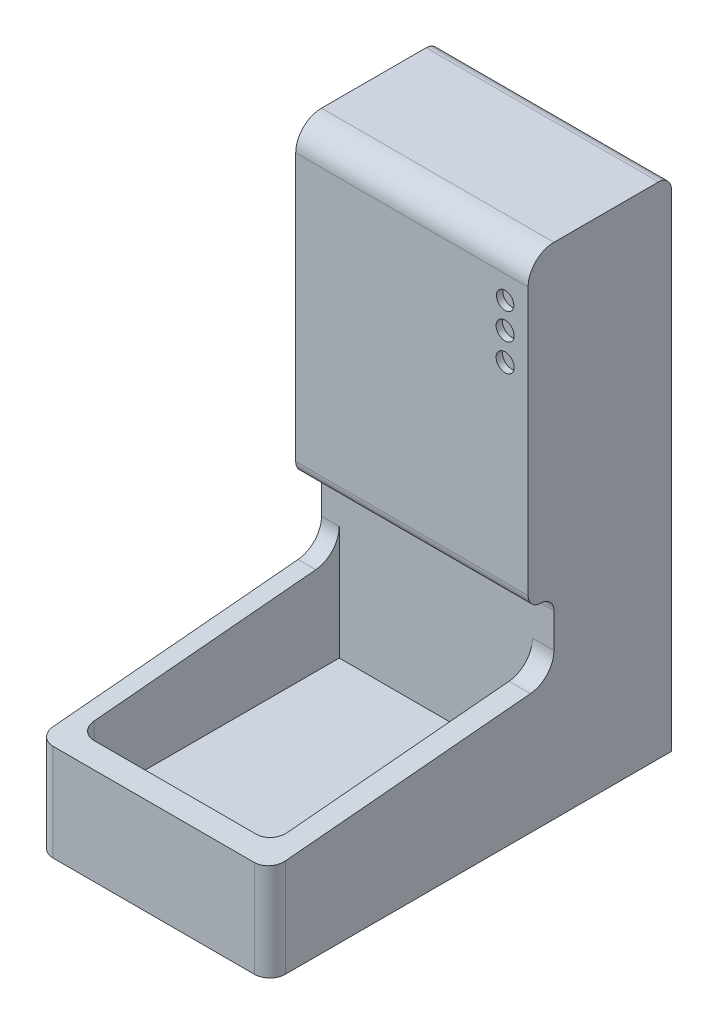
SolidWorks part; units mm, degrees
ref_plane "Front Plane" through (0, 0, 0) normal (0, 0, 1) x (1, 0, 0)
ref_plane "Top Plane" through (0, 0, 0) normal (0, 1, 0) x (1, 0, 0)
ref_plane "Right Plane" through (0, 0, 0) normal (1, 0, 0) x (0, 0, -1)
sketch "Sketch1" plane through (0, 0, 0) normal (1, 0, 0) x (0, 0, -1)
  line L0 (-1409.7, -4914.9) -> (-6489.7, -4914.9)
  line L1 (1409.7, -4914.9) -> (-1409.7, -4914.9)
  line L2 (1409.7, -4914.9) -> (1409.7, 4914.9)
  line L3 (1409.7, 4914.9) -> (-1409.7, 4914.9)
  line L4 (-1409.7, -1104.9) -> (-1409.7, 4914.9)
  line L5 (1409.7, -4914.9) -> (-1409.7, 4914.9) construction
  line L6 (1409.7, 4914.9) -> (-1409.7, -4914.9) construction
  line L7 (-1409.7, -1104.9) -> (-901.7, -1104.9)
  line L8 (-901.7, -1104.9) -> (-901.7, -3009.9)
  line L9 (-6489.7, -4914.9) -> (-6489.7, -3009.9)
  line L10 (-6489.7, -3009.9) -> (-901.7, -3009.9)
  point P0 (0, 0)
  dimension "D1" = 9829.8
  dimension "D2" = 2819.4
  dimension "D3" = 5080
  dimension "D4" = 3810
extrude "Boss-Extrude4" add sketch "Sketch1" along normal mid plane 4572
fillet "Fillet6" radius 508 1 edges at (0, 4914.9, 1409.7)
fillet "Fillet8" radius 254 2 edges at (0, 4914.9, -1409.7) (0, -1104.9, 1409.7)
sketch "Sketch5" plane through (0, -3009.9, 0) normal (0, 1, 0) x (1, 0, 0)
  line L0 (2286, -901.7) -> (-2286, -901.7) construction
  line L1 (-1878.0537, -901.7) -> (1863.9706, -901.7)
  line L2 (-1878.0537, -901.7) -> (-1878.0537, -5983.6143)
  line L3 (-1878.0537, -5983.6143) -> (1863.9706, -5983.6143)
  line L4 (1863.9706, -901.7) -> (1863.9706, -5983.6143)
fillet "Fillet13" radius 508 1 edges at (0, -3009.9, 901.7)
fillet "Fillet17" radius 254 1 edges at (0, -1104.9, 901.7)
sketch "Sketch6" plane through (0, 0, 1409.7) normal (0, 0, 1) x (1, 0, 0)
  circle A0 centre (1834.345, 3953.7453) radius 171.4502
  circle A1 centre (1834.345, 3439.3948) radius 178.0444
  circle A2 centre (1834.345, 2898.6674) radius 178.0444
extrude "Cut-Extrude6" cut sketch "Sketch6" against normal blind 127
sketch "Sketch7" plane through (2286, 0, 0) normal (1, 0, 0) x (0, 0, -1)
  line L0 (-6489.7, -3009.9) -> (-901.7, -2501.9)
  line L1 (-6489.7, -3009.9) -> (-901.7, -3009.9)
  line L2 (-901.7, -3009.9) -> (-5983.6143, -3009.9) construction
  line L3 (-901.7, -3009.9) -> (-5983.6143, -3009.9) construction
  line L4 (-901.7, -2501.9) -> (-901.7, -3009.9)
extrude "Boss-Extrude5" add sketch "Sketch7" against normal blind 4572
sketch "Sketch8" plane through (0, -4914.9, 0) normal (0, -1, 0) x (1, 0, 0)
  line L1 (-1937.2514, 6031.0036) -> (1863.9706, 6031.0036)
  line L2 (-1937.2514, 6031.0036) -> (-1937.2514, 901.7)
  line L3 (-1937.2514, 901.7) -> (1863.9706, 901.7)
  line L4 (1863.9706, 6031.0036) -> (1863.9706, 901.7)
extrude "Cut-Extrude7" cut sketch "Sketch8" against normal blind 2540
sketch "Sketch9" plane through (0, -4914.9, 0) normal (0, -1, 0) x (1, 0, 0)
  line L1 (-1937.2514, 6031.0036) -> (1863.9706, 6031.0036)
  line L2 (-1937.2514, 6031.0036) -> (-1937.2514, 901.7)
  line L3 (-1937.2514, 901.7) -> (1863.9706, 901.7)
  line L4 (1863.9706, 6031.0036) -> (1863.9706, 901.7)
extrude "Boss-Extrude6" add sketch "Sketch9" against normal blind 635
fillet "Fillet20" radius 304.8 4 edges at (1863.9706, -3624.0502, 6031.0036) (-1937.2514, -3624.0502, 6031.0036) (2286, -3962.4, 6489.7) (-2286, -3962.4, 6489.7)
fillet "Fillet22" radius 508 2 edges at (2074.9853, -2501.9, 901.7) (-2111.6257, -2501.9, 901.7)
